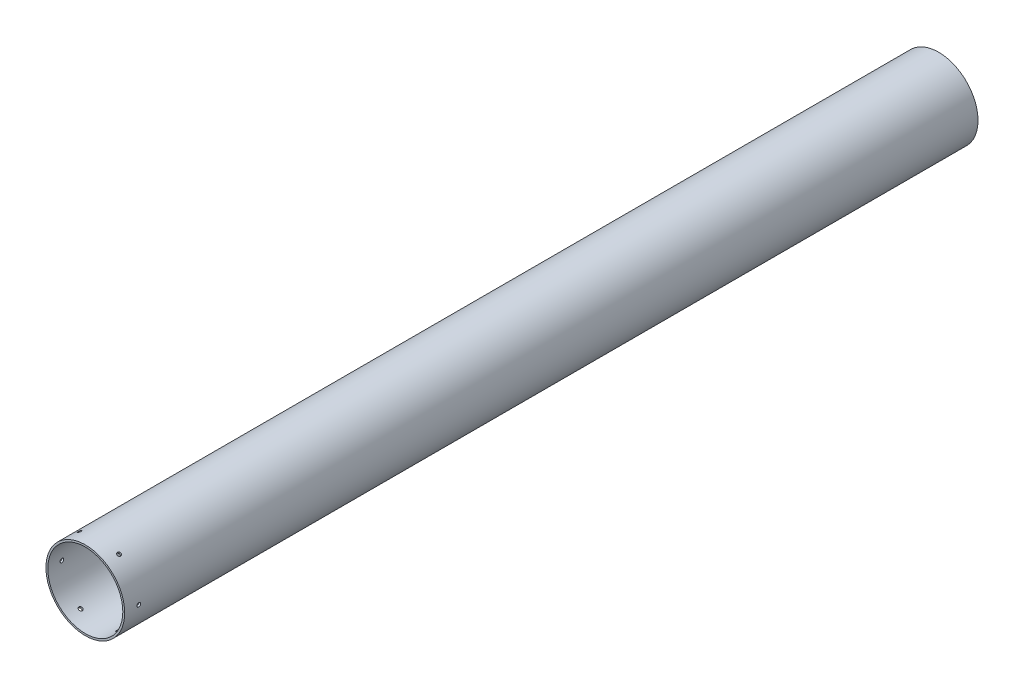
SolidWorks part; units mm, degrees
other "DetailItem1"
other "DetailItem2"
material "Default"
ref_plane "Front Plane" through (0, 0, 0) normal (0, 0, 1) x (1, 0, 0)
ref_plane "Top Plane" through (0, 0, 0) normal (0, 1, 0) x (1, 0, 0)
ref_plane "Right Plane" through (0, 0, 0) normal (1, 0, 0) x (0, 0, -1)
sketch "Sketch1" plane through (0, 0, 0) normal (1, 0, 0) x (0, 0, -1)
  line L0 (-455, 0) -> (455, 0) construction
  point P4 (0, 0)
  dimension "D1" = 910
ref_plane "Plane1" through (0, 0, 455) normal (0, 0, 1) x (1, 0, 0)
sketch "Sketch3" plane through (0, 0, 455) normal (0, 0, 1) x (1, 0, 0)
  circle A0 centre (0, 0) radius 42
  circle A1 centre (0, 0) radius 40
  dimension "D1" = 84
  dimension "D2" = 2
extrude "Boss-Extrude1" add sketch "Sketch3" against normal up to vertex (910 mm away) up to point (0, 0, -455)
ref_plane "Bolt Attachment" through (42, 0, 0) normal (1, 0, 0) x (0, 0, -1)
sketch "Sketch4" plane through (42, 0, 0) normal (1, 0, 0) x (0, 0, -1)
  line L0 (-455, 0) -> (-440, 0) construction
  line L1 (-455, 42) -> (-455, -42) construction
  circle A0 centre (-440, 0) radius 2
  dimension "D2" = 4
  dimension "D1" = 15
extrude "Cut-Extrude1" cut sketch "Sketch4" against normal up to surface (2 mm away) up to face at (40, 0, -455)
pattern_circular "CirPattern1" count 6 over 360 about axis through (0, 0, 455) along (0, 0, 1) of "Cut-Extrude1"
